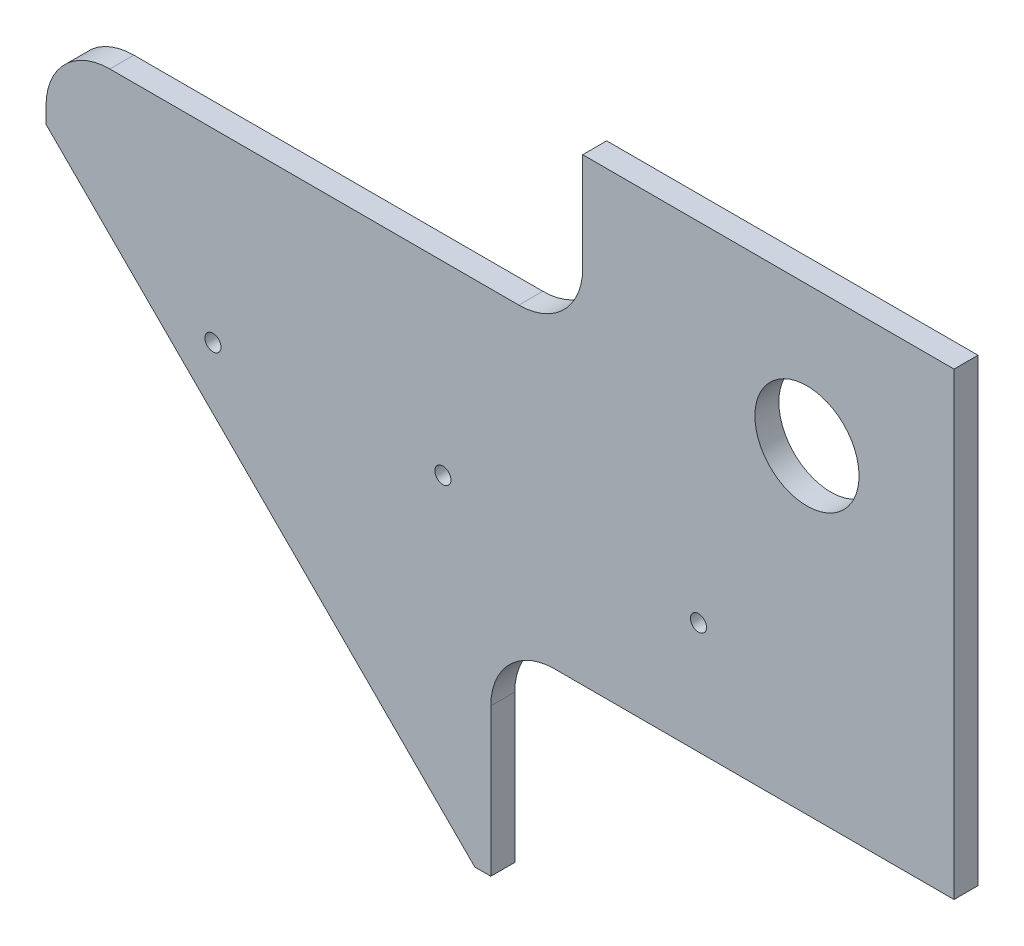
SolidWorks part; units mm, degrees
ref_plane "Front Plane" through (0, 0, 0) normal (0, 0, 1) x (1, 0, 0)
ref_plane "Top Plane" through (0, 0, 0) normal (0, 1, 0) x (1, 0, 0)
ref_plane "Right Plane" through (0, 0, 0) normal (1, 0, 0) x (0, 0, -1)
sketch "Sketch1" plane through (0, 0, 0) normal (0, 0, 1) x (1, 0, 0)
  line L0 (-138.2594, 48.9915) -> (32.2106, -121.4785)
  line L1 (32.2106, -121.4785) -> (222.7106, -121.4785)
  line L2 (-138.2594, 146.2068) -> (-138.2594, 48.9915)
  line L3 (-138.2594, 146.2068) -> (222.7106, 146.2068)
  line L4 (222.7106, -121.4785) -> (222.7106, 146.2068)
  circle A0 centre (164.2459, 89.532) radius 20.701
  circle A2 centre (164.2459, 89.532) radius 69.85 construction
  circle A3 centre (164.2459, 89.532) radius 302.5053 construction
  point P0 (0, 0)
  point P2 (164.2459, 89.532)
  dimension "D4" = 211.0105
  dimension "D1" = 45
  dimension "D2" = 267.6854
  dimension "D5" = 242.57
extrude "Boss-Extrude1" add sketch "Sketch1" along normal blind 9.525
sketch "Sketch2" plane through (0, 0, 9.525) normal (0, 0, 1) x (1, 0, 0)
  line L0 (32.2106, -121.4785) -> (222.7106, -121.4785) construction
  line L1 (222.7106, -121.4785) -> (38.5606, -121.4785)
  line L2 (222.7106, -121.4785) -> (222.7106, -37.4045)
  line L3 (222.7106, -37.4045) -> (38.5606, -37.4045)
  line L4 (38.5606, -121.4785) -> (38.5606, -37.4045)
extrude "Cut-Extrude1" cut sketch "Sketch2" against normal through all contours L3 L4 L1 L2
fillet "Fillet1" radius 25.4 1 edges at (38.5606, -37.4045, 4.7625)
sketch "Sketch4" plane through (0, 0, 9.525) normal (0, 0, 1) x (1, 0, 0)
  line L1 (-138.2594, 146.2068) -> (-138.2594, 48.9915) construction
  line L3 (-138.2594, 146.2068) -> (75.1006, 146.2068)
  line L4 (-138.2594, 146.2068) -> (-138.2594, 80.7415)
  line L5 (-138.2594, 80.7415) -> (75.1006, 80.7415)
  line L6 (75.1006, 146.2068) -> (75.1006, 80.7415)
extrude "Cut-Extrude2" cut sketch "Sketch4" against normal through all contours L5 L6 L3 L4
fillet "Fillet2" radius 25.4 2 edges at (-138.2594, 80.7415, 4.7625) (75.1006, 80.7415, 4.7625)
hole_wizard "Ø6.4 (6.4) Diameter Hole2" positions "Sketch15" profile "Sketch14" hole size "Ø6.4" standard "Lanco STD" end condition through all
sketch "Sketch15" plane through (0, 0, 0) normal (0, 0, -1) x (-1, 0, 0)
  point P3 (-121.1106, 7.0429)
  point P6 (-19.5106, 7.0429)
  point P9 (71.8957, 7.0429)
sketch "Sketch14" plane through (121.1106, 7.0429, 0) normal (1, 0, 0) x (0, 1, 0)
  line L0 (0, 0) -> (0, 9.525)
  line L1 (0, 9.525) -> (3.2, 9.525)
  line L2 (3.2, 9.525) -> (3.2, 0)
  line L5 (3.2, 0) -> (0, 0)
  line L11 (0, -6.35) -> (0, 107.95) construction
  dimension "Thru Hole Dia." = 6.4
  dimension "Thru Hole Depth" = 9.525
sketch "Sketch16" plane through (222.7106, 0, 0) normal (1, 0, 0) x (0, 0, -1)
  line L0 (0, -37.4045) -> (0, 146.2068) construction
  line L1 (-9.525, 146.2068) -> (0, 146.2068)
  line L2 (-9.525, 146.2068) -> (-9.525, 145.2215)
  line L3 (-9.525, 145.2215) -> (0, 145.2215)
  line L4 (0, 146.2068) -> (0, 145.2215)
extrude "Cut-Extrude3" cut sketch "Sketch16" against normal through all
